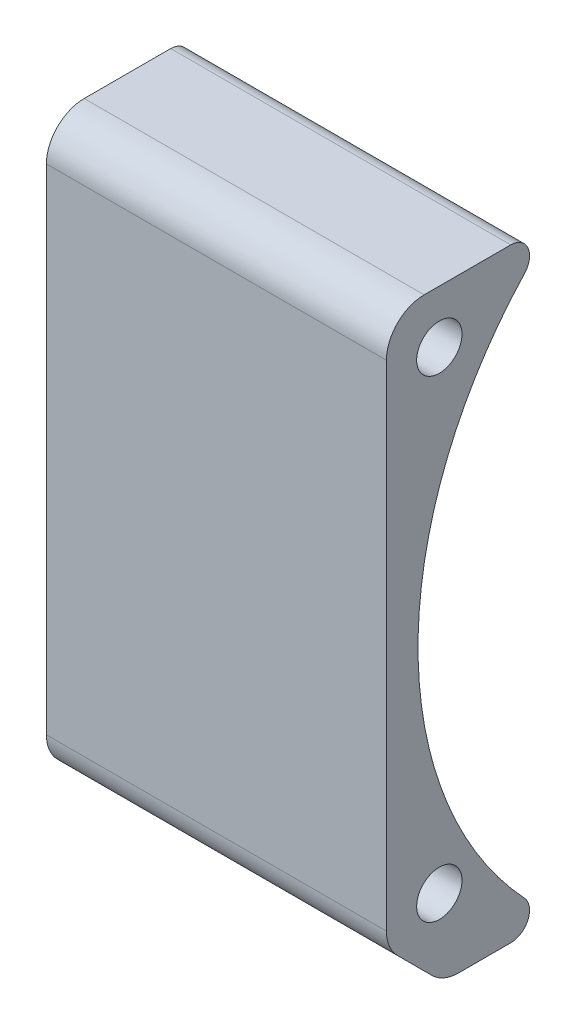
SolidWorks part; units mm, degrees
ref_plane "Front Plane" through (0, 0, 0) normal (0, 0, 1) x (1, 0, 0)
ref_plane "Top Plane" through (0, 0, 0) normal (0, 1, 0) x (1, 0, 0)
ref_plane "Right Plane" through (0, 0, 0) normal (1, 0, 0) x (0, 0, -1)
sketch "Sketch1" plane through (0, 0, 0) normal (1, 0, 0) x (0, 0, -1)
  line L0 (0, 0) -> (0, 50.8)
  line L1 (0, 50.8) -> (14.3998, 50.8)
  line L2 (0, 0) -> (14.3998, 0)
  arc A0 (14.3998, 50.8) -> (14.3998, 0) centre (35.9921, 25.4) ccw
  dimension "D1" = 50.8
  dimension "D2" = 66.675
extrude "Boss-Extrude1" add sketch "Sketch1" along normal blind 28.575
chamfer "Chamfer1" distance 4.7625 angle 45 1 edges at (14.2875, 0, 0)
fillet "Fillet1" radius 3.175 3 edges at (14.2875, 4.7625, 0) (14.2875, 0, -4.7625) (14.2875, 50.8, 0)
fillet "Fillet2" radius 1.5875 2 edges at (14.2875, 50.8, -14.3998) (14.2875, 0, -14.3998)
sketch "Sketch2" plane through (28.575, 0, 0) normal (1, 0, 0) x (0, 0, -1)
  line L0 (10.4437, 50.8) -> (3.175, 50.8) construction
  line L1 (0, 47.625) -> (0, 6.0776) construction
  line L2 (0.9299, 3.8326) -> (3.8326, 0.9299) construction
  circle A0 centre (4.445, 46.355) radius 4.445 construction
  circle A1 centre (4.445, 6.6037) radius 4.445 construction
  point P0 (4.445, 46.355)
  point P2 (4.445, 6.6037)
  dimension "D1" = 8.89
hole_wizard "#8 Clearance Hole1" positions "Sketch2" profile "Sketch3" hole size "#8" standard "ANSI Inch" end condition through all
sketch "Sketch3" plane through (28.575, 46.355, -4.445) normal (0, 1, 0) x (0, 0, -1)
  line L0 (0, 0) -> (0, 28.575)
  line L1 (0, 28.575) -> (1.905, 28.575)
  line L2 (1.905, 28.575) -> (1.905, 0)
  line L5 (1.905, 0) -> (0, 0)
  line L11 (0, -6.35) -> (0, 107.95) construction
  dimension "Thru Hole Dia." = 3.81
  dimension "Thru Hole Depth" = 28.575
